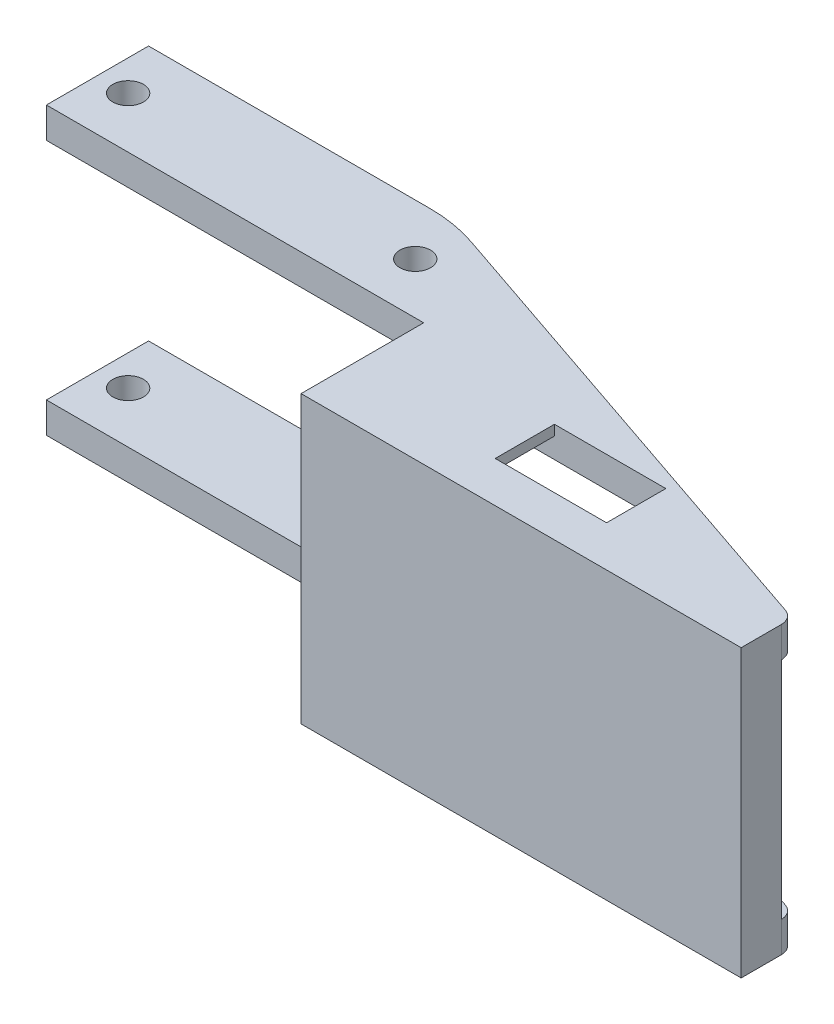
SolidWorks part; units mm, degrees
material "ABS"
ref_plane "Front Plane" through (0, 0, 0) normal (0, 0, 1) x (1, 0, 0)
ref_plane "Top Plane" through (0, 0, 0) normal (0, 1, 0) x (1, 0, 0)
ref_plane "Right Plane" through (0, 0, 0) normal (1, 0, 0) x (0, 0, -1)
sketch "Sketch1" plane through (0, 0, 0) normal (0, 1, 0) x (1, 0, 0)
  line L0 (-4.5779, 9.3563) -> (42.0567, -6.4995)
  line L1 (-36.9262, 10.1547) -> (-9.4065, 10.1547)
  line L2 (-36.9262, 10.1547) -> (-36.9262, 0.1547)
  line L3 (0, -11.8453) -> (43.0738, -11.8453)
  line L4 (43.0738, -7.9196) -> (43.0738, -11.8453)
  line L5 (-36.9262, 10.1547) -> (43.0738, -11.8453) construction
  line L6 (-3.5929, 0.1547) -> (26.2671, -1.131) construction
  line L10 (-36.9262, 0.1547) -> (0, 0.1547)
  line L11 (0, -11.8453) -> (0, 0.1547)
  arc A0 (-9.4065, 10.1547) -> (-4.5779, 9.3563) centre (-9.4065, -4.8453) cw
  arc A1 (42.0567, -6.4995) -> (43.0738, -7.9196) centre (41.5738, -7.9196) cw
  point P0 (0, 0)
  point P10 (-6.9262, 10.1547)
  point P13 (43.0738, -6.8453)
  dimension "D6" = 15
  dimension "D7" = 1.5
  dimension "D1" = 10
  dimension "D2" = 80
  dimension "D3" = 5
  dimension "D4" = 50
  dimension "D5" = 10.7143
  dimension "D8" = 12
  dimension "D9" = 33.3333
extrude "Boss-Extrude1" add sketch "Sketch1" against normal blind 3
extrude "Boss-Extrude2" add sketch "Sketch1<2>" along normal blind 3 from offset 22 separate body
sketch "Sketch1<2>" plane through (0, 0, 0) normal (0, 1, 0) x (1, 0, 0) same geometry as "Sketch1"
hole_wizard "Ø3.0mm Clearance Dowel Hole1" positions "Sketch2" profile "Sketch3" hole size "Ø3.0" standard "ANSI Metric" end condition through all
sketch "Sketch2" plane through (0, -3, 0) normal (0, -1, 0) x (-1, 0, 0)
  line L0 (36.9262, 10.1547) -> (36.9262, 0.1547) construction
  point P0 (33.9262, 5.1547)
  point P2 (5.8262, 5.1547)
  point P7 (36.9262, 5.1547)
  dimension "D1" = 3
  dimension "D2" = 28.1
sketch "Sketch3" plane through (-33.9262, -3, -5.1547) normal (1, 0, 0) x (0, 0, -1)
  line L0 (0, 0) -> (0, 28)
  line L1 (0, 28) -> (1.5, 28)
  line L2 (1.5, 28) -> (1.5, 0)
  line L5 (1.5, 0) -> (0, 0)
  line L11 (0, -6.35) -> (0, 107.95) construction
  dimension "Thru Hole Dia." = 3
  dimension "Thru Hole Depth" = 28
sketch "Sketch5" plane through (0, 0, 0) normal (0, 1, 0) x (1, 0, 0)
  line L1 (0, -11.8453) -> (43.0738, -11.8453)
  line L2 (0, -11.8453) -> (0, -7.9196)
  line L3 (0, -7.9196) -> (43.0738, -7.9196)
  line L4 (43.0738, -11.8453) -> (43.0738, -7.9196)
extrude "Boss-Extrude3" add sketch "Sketch5" along normal up to surface (22 mm away) up to face at (-33.9262, 22, -6.6547)
sketch "Sketch6" plane through (0, 25, 0) normal (0, 1, 0) x (1, 0, 0)
  line L0 (0, -11.8453) -> (43.0738, -11.8453) construction
  line L1 (13, -2.0453) -> (25.9, -2.0453)
  line L2 (13, -2.0453) -> (13, -7.8453)
  line L3 (13, -7.8453) -> (25.9, -7.8453)
  line L4 (25.9, -2.0453) -> (25.9, -7.8453)
  line L5 (0, 0.1547) -> (0, -11.8453) construction
  dimension "D1" = 12.9
  dimension "D2" = 5.8
  dimension "D3" = 4
  dimension "D4" = 13
extrude "Cut-Extrude1" cut sketch "Sketch6" against normal blind 10
sketch "Sketch7" plane through (13, 0, 0) normal (1, 0, 0) x (0, 0, -1)
  line L0 (-6.4995, 25) -> (9.3563, 25) construction
  line L1 (-7.8453, 25) -> (-2.0453, 25)
  line L2 (-7.8453, 25) -> (-7.8453, 24)
  line L3 (-7.8453, 24) -> (-2.0453, 24)
  line L4 (-2.0453, 25) -> (-2.0453, 24)
  line L5 (-7.8453, 22) -> (-7.8453, 25) construction
  line L6 (-2.0453, 22) -> (-2.0453, 25) construction
  dimension "D1" = 1
extrude "Boss-Extrude4" add sketch "Sketch7" along normal blind 2
